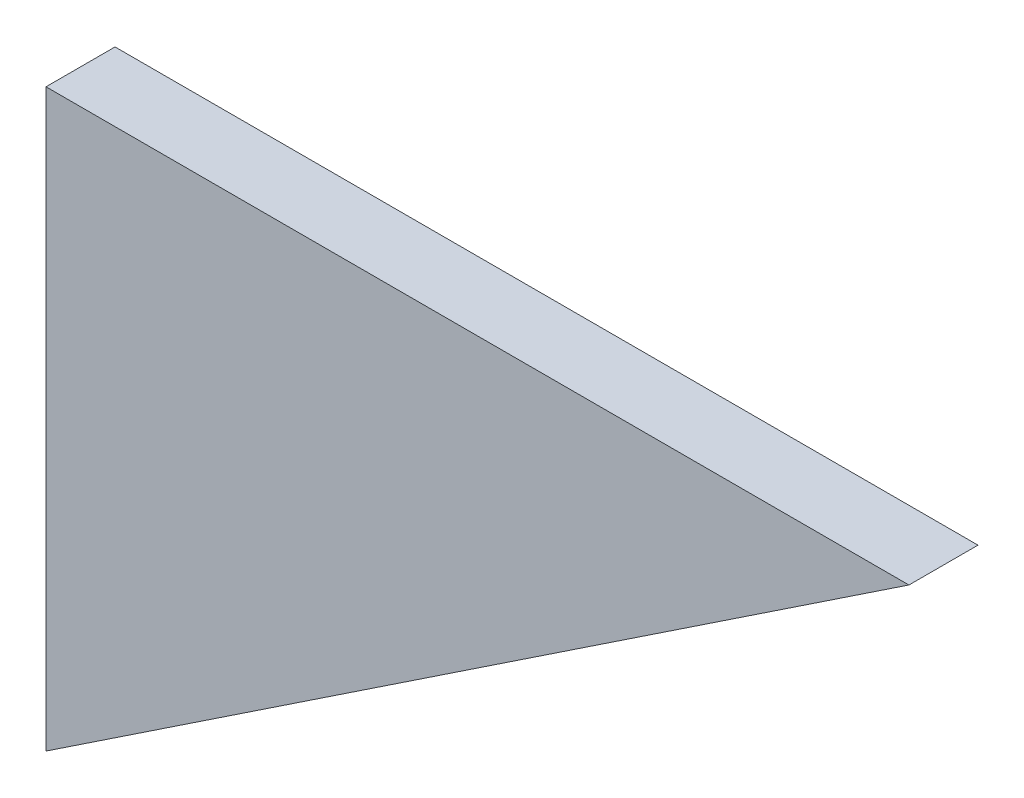
SolidWorks part; units mm, degrees
material "Клен"
ref_plane "Спереди" through (0, 0, 0) normal (0, 0, 1) x (1, 0, 0)
ref_plane "Сверху" through (0, 0, 0) normal (0, 1, 0) x (1, 0, 0)
ref_plane "Справа" through (0, 0, 0) normal (1, 0, 0) x (0, 0, -1)
sketch "Эскиз1" plane through (0, 0, 0) normal (0, 0, 1) x (1, 0, 0)
  line L5 (6, -293.8462) -> (6, -343.8462)
  line L7 (6, -343.8462) -> (81, -293.8462)
  line L9 (81, -293.8462) -> (6, -293.8462)
  dimension "D1" = 50
  dimension "D2" = 75
extrude "Бобышка-Вытянуть1" add sketch "Эскиз1" against normal blind 6 contours L7 L9 L5
